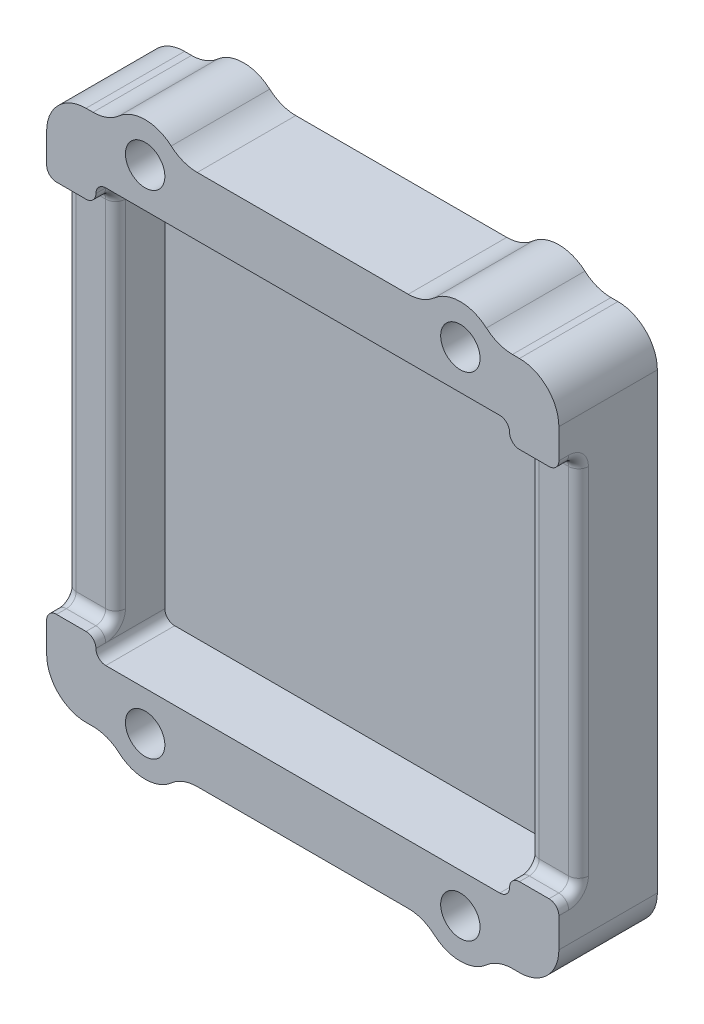
SolidWorks part; units mm, degrees
ref_plane "Plan de face" through (0, 0, 0) normal (0, 0, 1) x (1, 0, 0)
ref_plane "Plan de dessus" through (0, 0, 0) normal (0, 1, 0) x (1, 0, 0)
ref_plane "Plan de droite" through (0, 0, 0) normal (1, 0, 0) x (0, 0, -1)
sketch "Esquisse1" plane through (0, 0, 0) normal (0, 0, 1) x (1, 0, 0)
  line L0 (0, 0) -> (0, 13.5) construction
  line L1 (10.5, 10.5) -> (-10.5, 10.5)
  line L2 (10.5, 10.5) -> (10.5, -10.5)
  line L3 (10.5, -10.5) -> (-10.5, -10.5)
  line L4 (-10.5, 10.5) -> (-10.5, -10.5)
  line L5 (10.5, 10.5) -> (-10.5, -10.5) construction
  line L6 (10.5, -10.5) -> (-10.5, 10.5) construction
  line L7 (13, 13.5) -> (9.7321, 13.5)
  line L8 (13, 13.5) -> (13, -13.5)
  line L9 (13, -13.5) -> (9.7321, -13.5)
  line L10 (-13, 13.5) -> (-13, -13.5)
  line L11 (13, 13.5) -> (-13, -13.5) construction
  line L12 (13, -13.5) -> (-13, 13.5) construction
  line L13 (0, 0) -> (13, 0) construction
  line L14 (-9.7321, 13.5) -> (-13, 13.5)
  line L15 (6.2679, 13.5) -> (-6.2679, 13.5)
  line L16 (-9.7321, -13.5) -> (-13, -13.5)
  line L17 (6.2679, -13.5) -> (-6.2679, -13.5)
  circle A0 centre (-8, 12.5) radius 1
  circle A1 centre (8, 12.5) radius 1
  circle A2 centre (8, -12.5) radius 1
  circle A3 centre (-8, -12.5) radius 1
  arc A4 (-6.2679, 13.5) -> (-9.7321, 13.5) centre (-8, 12.5) ccw
  arc A5 (9.7321, 13.5) -> (6.2679, 13.5) centre (8, 12.5) ccw
  arc A6 (-9.7321, -13.5) -> (-6.2679, -13.5) centre (-8, -12.5) ccw
  arc A7 (6.2679, -13.5) -> (9.7321, -13.5) centre (8, -12.5) ccw
  point P0 (0, 0)
  point P6 (0, 0)
  dimension "D6" = 2
  dimension "D7" = 25
  dimension "D1" = 21
  dimension "D2" = 21
  dimension "D3" = 2.5
  dimension "D4" = 2.5
  dimension "D5" = 3
  dimension "D8" = 16
extrude "Boss.-Extru.1" add sketch "Esquisse1" along normal blind 5
sketch "Esquisse2" plane through (0, 0, 0) normal (0, 0, -1) x (-1, 0, 0)
  line L1 (10.5, 10.5) -> (-10.5, 10.5)
  line L2 (10.5, 10.5) -> (10.5, -10.5)
  line L3 (10.5, -10.5) -> (-10.5, -10.5)
  line L4 (-10.5, 10.5) -> (-10.5, -10.5)
  line L5 (10.5, 10.5) -> (-10.5, -10.5) construction
  line L6 (10.5, -10.5) -> (-10.5, 10.5) construction
  point P4 (0, 0)
extrude "Boss.-Extru.2" add sketch "Esquisse2" against normal blind 1.5
sketch "Esquisse3" plane through (0, 0, 5) normal (0, 0, 1) x (1, 0, 0)
  line L0 (-13, 13.5) -> (-13, -13.5) construction
  line L1 (-13, 9.5) -> (-10.5, 9.5)
  line L2 (-13, 9.5) -> (-13, -9.5)
  line L3 (-13, -9.5) -> (-10.5, -9.5)
  line L4 (-10.5, 9.5) -> (-10.5, -9.5)
  line L5 (-13, 9.5) -> (-10.5, -9.5) construction
  line L6 (-13, -9.5) -> (-10.5, 9.5) construction
  line L7 (-10.5, 10.5) -> (-10.5, -10.5) construction
  line L8 (0, 13.5) -> (0, -13.5) construction
  line L9 (6.2679, 13.5) -> (-6.2679, 13.5) construction
  line L10 (-6.2679, -13.5) -> (6.2679, -13.5) construction
  line L11 (13, -9.5) -> (10.5, 9.5) construction
  line L12 (13, 9.5) -> (10.5, -9.5) construction
  line L13 (10.5, 9.5) -> (10.5, -9.5)
  line L14 (13, -9.5) -> (10.5, -9.5)
  line L15 (13, 9.5) -> (13, -9.5)
  line L16 (13, 9.5) -> (10.5, 9.5)
  line L17 (0, 0) -> (11.75, 0) construction
  point P4 (-11.75, 0)
  point P19 (11.75, 0)
  dimension "D1" = 19
extrude "Enlèv. mat.-Extru.1" cut sketch "Esquisse3" against normal blind 1
fillet "Congé1" radius 2 4 edges at (-13, 13.5, 2.5) (-13, -13.5, 2.5) (13, -13.5, 2.5) (13, 13.5, 2.5)
fillet "Congé2" radius 2 8 edges at (-9.7321, -13.5, 2.5) (-6.2679, -13.5, 2.5) (6.2679, -13.5, 2.5) (9.7321, -13.5, 2.5) (9.7321, 13.5, 2.5) (6.2679, 13.5, 2.5) (-6.2679, 13.5, 2.5) (-9.7321, 13.5, 2.5)
fillet "Congé3" radius 0.5 20 edges at (13, -9.5, 4.5) (-13, 9.5, 4.5) (-13, -9.5, 4.5) (-10.5, -9.5, 4.5) (-10.5, 9.5, 4.5) (10.5, 9.5, 4.5) (10.5, -9.5, 4.5) (13, 0, 4) (-13, 0, 4) (-10.5, 0, 4) (10.5, 0, 4) (13, 9.5, 4.5) (11.75, -9.5, 4) (11.75, 9.5, 4) (-11.75, 9.5, 4) (-11.75, -9.5, 4) (-10.5, -10.5, 3.25) (10.5, -10.5, 3.25) (10.5, 10.5, 3.25) (-10.5, 10.5, 3.25)
sketch "Esquisse4" [suppressed] plane through (0, 0, 0) normal (0, 0, -1) x (-1, 0, 0)
  line L0 (10.5, -10) -> (10.5, 10) construction
  line L1 (-3.5, 10.5) -> (10.5, 10.5)
  line L2 (-3.5, 10.5) -> (-3.5, 7.5)
  line L3 (-3.5, 7.5) -> (10.5, 7.5)
  line L4 (10.5, 10.5) -> (10.5, 7.5)
  line L5 (-3.5, 10.5) -> (10.5, 7.5) construction
  line L6 (-3.5, 7.5) -> (10.5, 10.5) construction
  line L7 (10, 10.5) -> (-10, 10.5) construction
  point P4 (3.5, 9)
  dimension "D1" = 14
  dimension "D2" = 3
extrude "Enlèv. mat.-Extru.2" [suppressed] cut sketch "Esquisse4" against normal through all
fillet "Congé4" [suppressed] radius 0.5
sketch "Esquisse5" [suppressed] plane through (0, 0, 0) normal (0, 0, -1) x (-1, 0, 0)
  line L0 (13, 11.5) -> (13, -11.5) construction
  line L1 (8, 4.5) -> (13, 4.5)
  line L2 (8, 4.5) -> (8, -9.5)
  line L3 (8, -9.5) -> (13, -9.5)
  line L4 (13, 4.5) -> (13, -9.5)
  line L5 (8, 4.5) -> (13, -9.5) construction
  line L6 (8, -9.5) -> (13, 4.5) construction
  line L7 (11, -9.5) -> (12.5, -9.5) construction
  point P4 (10.5, -2.5)
  dimension "D1" = 5
  dimension "D2" = 14
extrude "Enlèv. mat.-Extru.3" [suppressed] cut sketch "Esquisse5" against normal through all
fillet "Congé5" [suppressed] radius 0.5
